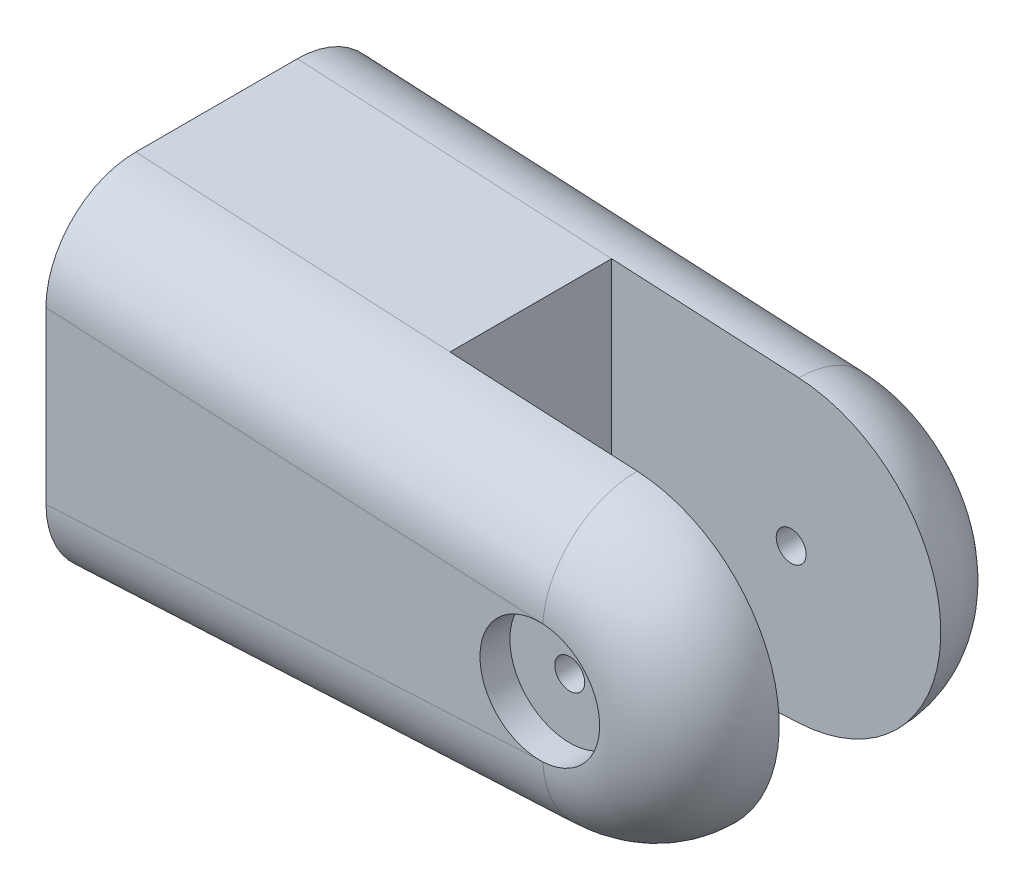
SolidWorks part; units mm, degrees
ref_plane "Front Plane" through (0, 0, 0) normal (0, 0, 1) x (1, 0, 0)
ref_plane "Top Plane" through (0, 0, 0) normal (0, 1, 0) x (1, 0, 0)
ref_plane "Right Plane" through (0, 0, 0) normal (1, 0, 0) x (0, 0, -1)
sketch "Sketch1" plane through (0, 0, 0) normal (0, 0, 1) x (1, 0, 0)
  line L0 (0, 0) -> (-165, 0) construction
  line L1 (-165, -58.5) -> (-165, 58.5)
  line L2 (2.5526, 49.9348) -> (-165, 58.5)
  line L3 (2.5526, -49.9348) -> (-165, -58.5)
  arc A0 (2.5526, -49.9348) -> (2.5526, 49.9348) centre (0, 0) ccw
  dimension "D1" = 100
  dimension "D2" = 165
  dimension "D3" = 58.5
extrude "Boss-Extrude1" add sketch "Sketch1" along normal mid plane 114
sketch "Sketch2" plane through (-165, 0, 0) normal (-1, 0, 0) x (0, 0, 1)
  circle A0 centre (0, 0) radius 37.5
  dimension "D1" = 75
extrude "Boss-Extrude2" add sketch "Sketch2" along normal blind 2
sketch "Sketch3" plane through (0, 0, 0) normal (0, 1, 0) x (1, 0, 0)
  line L0 (50, 0) -> (50, -27)
  line L1 (50, -57) -> (50, 57) construction
  line L2 (50, -27) -> (50, 27)
  line L3 (50, 27) -> (-60, 27)
  line L4 (-60, 27) -> (-60, -27)
  line L5 (-60, -27) -> (50, -27)
  dimension "D1" = 27
  dimension "D2" = 54
  dimension "D3" = 110
  dimension "D4" = 54
  dimension "D5" = 110
extrude "Cut-Extrude1" cut sketch "Sketch3" against normal through all both and the other way through all contours L4 L5 L0 L2 L3 region at (-5, 0, 0)
fillet "Fillet2" radius 30 6 edges at (-81.2237, -54.2174, 57) (-81.2237, -54.2174, -57) (50, 0, -57) (-81.2237, 54.2174, -57) (-81.2237, 54.2174, 57) (50, 0, 57)
sketch "Sketch5" plane through (0, 0, -57) normal (0, 0, -1) x (-1, 0, 0)
  circle A0 centre (0, 0) radius 20
extrude "Cut-Extrude2" cut sketch "Sketch5" against normal blind 10
mirror "Mirror1" about plane through (0, 0, 0) normal (0, 0, 1) of "Cut-Extrude2"
sketch "Sketch6" plane through (0, 0, -47) normal (0, 0, -1) x (-1, 0, 0)
  circle A0 centre (0, 0) radius 5
extrude "Cut-Extrude3" cut sketch "Sketch6" against normal blind 500
